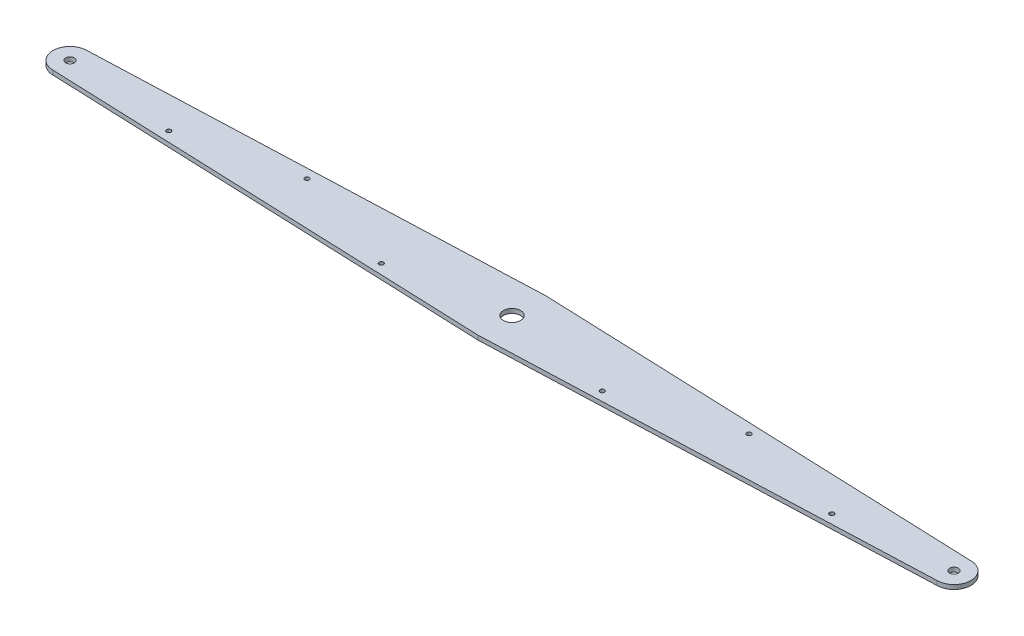
SolidWorks part; units mm, degrees
ref_plane "Front Plane" through (0, 0, 0) normal (0, 0, 1) x (1, 0, 0)
ref_plane "Top Plane" through (0, 0, 0) normal (0, 1, 0) x (1, 0, 0)
ref_plane "Right Plane" through (0, 0, 0) normal (1, 0, 0) x (0, 0, -1)
sketch "Sketch2" plane through (0, 0, 0) normal (0, 1, 0) x (1, 0, 0)
  line L0 (0, 0) -> (0, 25) construction
  line L1 (0, 0) -> (0, -25) construction
  line L2 (0, 0) -> (-325, 0) construction
  line L3 (-325, 12.5) -> (0, 25)
  line L4 (-325, -12.5) -> (0, -25)
  line L5 (325, -12.5) -> (0, -25)
  line L6 (325, 12.5) -> (0, 25)
  arc A0 (-325, 12.5) -> (-325, -12.5) centre (-325, 0) ccw
  arc A1 (325, 12.5) -> (325, -12.5) centre (325, 0) cw
  dimension "D2" = 25
  dimension "D1" = 50
  dimension "Half of Chassis Width" = 325
extrude "Boss-Extrude1" add sketch "Sketch2" along normal blind 3.18
sketch "Sketch3" plane through (0, 3.18, 0) normal (0, 1, 0) x (1, 0, 0)
  line L0 (0, 25) -> (0, -25) construction
  line L1 (-325, 0) -> (0, 0) construction
  line L2 (-243.75, -8.625) -> (-243.75, 0) construction
  line L3 (-162.5, 11.75) -> (-162.5, 0) construction
  line L4 (-81.25, -14.875) -> (-81.25, 0) construction
  line L5 (-243.75, -8.625) -> (-243.75, -15.625) construction
  line L6 (-325, -12.5) -> (0, -25) construction
  line L7 (-162.5, 11.75) -> (-162.5, 18.75) construction
  line L8 (0, 25) -> (-325, 12.5) construction
  line L9 (-81.25, -14.875) -> (-81.25, -21.875) construction
  circle A0 centre (0, 0) radius 6.35
  circle A1 centre (-325, 0) radius 3.175
  circle A2 centre (-243.75, -8.625) radius 1.65
  circle A3 centre (-162.5, 11.75) radius 1.65
  circle A4 centre (-81.25, -14.875) radius 1.65
  circle A5 centre (81.25, -14.875) radius 1.65
  circle A6 centre (162.5, 11.75) radius 1.65
  circle A7 centre (243.75, -8.625) radius 1.65
  circle A8 centre (325, 0) radius 3.175
  dimension "D1" = 12.7
  dimension "D2" = 6.35
  dimension "D3" = 3.3
  dimension "Hole3" = 243.75
  dimension "Hole2" = 162.5
  dimension "Hole1" = 81.25
  dimension "D4" = 7
  dimension "D5" = 7
  dimension "D6" = 7
extrude "Cut-Extrude1" cut sketch "Sketch3" against normal through all
equation "\"Half of Chassis Width@Sketch2\"= \"Chassis Width@Differential System Assy - Option 1.Assembly\" / 2"
equation "\"Hole3@Sketch3\"= \"Chassis Width@Differential System Assy - Option 1.Assembly\" / 2 * 0.75"
equation "\"Hole2@Sketch3\"= \"Chassis Width@Differential System Assy - Option 1.Assembly\" / 2 * 0.5"
equation "\"Hole1@Sketch3\"= \"Chassis Width@Differential System Assy - Option 1.Assembly\" / 2 * 0.25"
